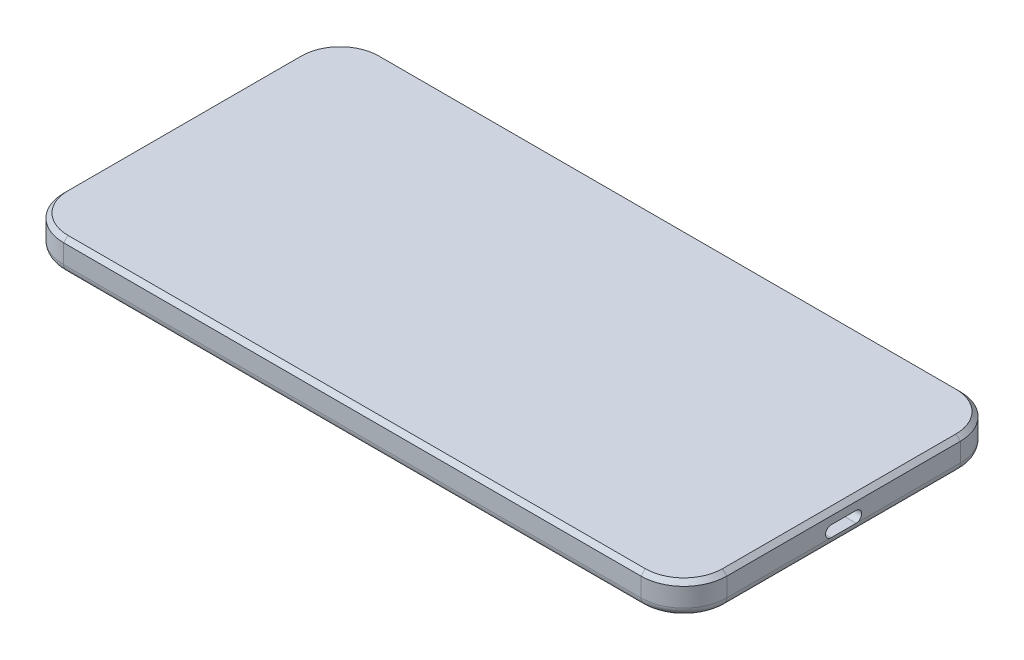
SolidWorks part; units mm, degrees
ref_plane "Front Plane" through (0, 0, 0) normal (0, 0, 1) x (1, 0, 0)
ref_plane "Top Plane" through (0, 0, 0) normal (0, 1, 0) x (1, 0, 0)
ref_plane "Right Plane" through (0, 0, 0) normal (1, 0, 0) x (0, 0, -1)
sketch "Sketch1" plane through (0, 0, 0) normal (0, 1, 0) x (1, 0, 0)
  line L1 (-77.25, 37.2) -> (77.25, 37.2)
  line L2 (-77.25, 37.2) -> (-77.25, -37.2)
  line L3 (-77.25, -37.2) -> (77.25, -37.2)
  line L4 (77.25, 37.2) -> (77.25, -37.2)
  line L5 (-77.25, 37.2) -> (77.25, -37.2) construction
  line L6 (-77.25, -37.2) -> (77.25, 37.2) construction
  point P0 (0, 0)
  dimension "D1" = 154.5
  dimension "D2" = 74.4
extrude "Boss-Extrude1" add sketch "Sketch1" along normal blind 7.4
fillet "Fillet1" radius 10 4 edges at (-77.25, 3.7, -37.2) (77.25, 3.7, -37.2) (-77.25, 3.7, 37.2) (77.25, 3.7, 37.2)
chamfer "Chamfer1" distance 1 angle 45 8 edges at (0, 7.4, 37.2) (74.3211, 7.4, 34.2711) (-74.3211, 7.4, 34.2711) (77.25, 7.4, 0) (-77.25, 7.4, 0) (74.3211, 7.4, -34.2711) (-74.3211, 7.4, -34.2711) (0, 7.4, -37.2)
fillet "Fillet2" radius 2 8 edges at (74.3211, 0, -34.2711) (77.25, 0, 0) (74.3211, 0, 34.2711) (0, 0, 37.2) (-74.3211, 0, 34.2711) (-77.25, 0, 0) (-74.3211, 0, -34.2711) (0, 0, -37.2)
sketch "Sketch2" plane through (0, 0, 0) normal (0, -1, 0) x (1, 0, 0)
  line L0 (-68.95, -35.2) -> (-68.95, 35.2) construction
  line L1 (-67.25, -35.2) -> (67.25, -35.2) construction
  line L2 (67.25, 35.2) -> (-67.25, 35.2) construction
  line L3 (-68.95, -9.45) -> (-68.95, -27.95) construction
  line L4 (-73.25, -23.65) -> (-73.25, -13.75)
  line L5 (-64.65, -13.75) -> (-64.65, -23.65)
  line L6 (-77.25, -27.2) -> (-77.25, 27.2) construction
  line L7 (67.25, -37.2) -> (-67.25, -37.2) construction
  circle A0 centre (-68.95, -13.75) radius 4.3
  circle A1 centre (-68.95, -23.65) radius 4.3
  dimension "D1" = 18.5
  dimension "D2" = 4
  dimension "D3" = 8.6
  dimension "D4" = 9.25
extrude "Boss-Extrude2" add sketch "Sketch2" along normal blind 0.6 contours A0 | A1 L5 A0 L4 | A1 region at (-68.95, 0, -18.7) region at (-68.95, 0, -23.65) region at (-68.95, 0, -13.75)
chamfer "Chamfer2" distance 0.3 angle 45 4 edges at (-64.65, -0.6, -18.7) (-68.95, -0.6, -27.95) (-68.95, -0.6, -9.45) (-73.25, -0.6, -18.7)
sketch "Sketch3" plane through (77.25, 0, 0) normal (1, 0, 0) x (0, 0, -1)
  line L0 (0, 0) -> (0, 7.4) construction
  line L1 (-27.2, 7.4) -> (27.2, 7.4) construction
  line L2 (-2.9, 3.3) -> (2.9, 3.3) construction
  line L3 (-2.9, 4.6) -> (2.9, 4.6)
  line L4 (-2.9, 2) -> (2.9, 2)
  line L5 (-4.2, 3.3) -> (4.2, 3.3) construction
  line L7 (-27.2, 2) -> (27.2, 2) construction
  arc A0 (-2.9, 4.6) -> (-2.9, 2) centre (-2.9, 3.3) ccw
  arc A1 (2.9, 2) -> (2.9, 4.6) centre (2.9, 3.3) ccw
  point P7 (0, 3.3)
  dimension "D1" = 8.4
  dimension "D2" = 2.6
extrude "Cut-Extrude1" cut sketch "Sketch3" against normal blind 6.75
